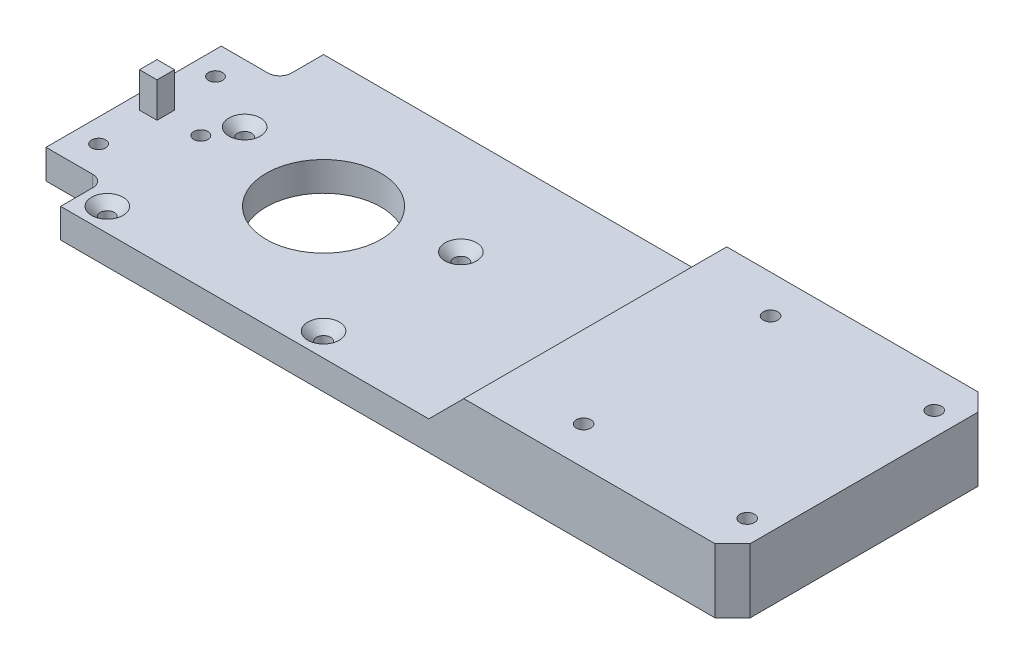
SolidWorks part; units mm, degrees
material "7075-T6, Plate (SS)"
ref_plane "Front Plane" through (0, 0, 0) normal (0, 0, 1) x (1, 0, 0)
ref_plane "Top Plane" through (0, 0, 0) normal (0, 1, 0) x (1, 0, 0)
ref_plane "Right Plane" through (0, 0, 0) normal (1, 0, 0) x (0, 0, -1)
sketch "Sketch1" plane through (0, 0, 0) normal (0, 1, 0) x (1, 0, 0)
  line L1 (0, -22.5) -> (115, -22.5)
  line L2 (0, -22.5) -> (0, 22.5)
  line L3 (0, 22.5) -> (115, 22.5)
  line L4 (115, -22.5) -> (115, 22.5)
  dimension "D1" = 45
  dimension "D2" = 115
extrude "Boss-Extrude1" add sketch "Sketch1" along normal blind 5 contours L2 L3 L4 L1
sketch "Sketch2" plane through (0, 5, 0) normal (0, 1, 0) x (1, 0, 0)
  line L0 (0, -22.5) -> (0, 22.5) construction
  circle A0 centre (22.5, 0) radius 9.8171
  dimension "D2" = 19.6342
  dimension "D1" = 22.5
extrude "Cut-Extrude1" cut sketch "Sketch2" against normal up to next
cosmetic thread "Cosmetic Thread1" parameters "D2"=20.32
hole_wizard "CSK for M2 Countersunk Flat Head Screw1" positions "Sketch3" profile "Sketch4" countersink size "M2" standard "DIN" end condition through all
sketch "Sketch3" plane through (0, 5, 0) normal (0, 1, 0) x (1, 0, 0)
  line L2 (0, -22.5) -> (115, -22.5) construction
  point P6 (4, -18.5)
  point P48 (41, -18.5)
  point P50 (41, 5)
  point P52 (4, 5)
  dimension "D3" = 4
  dimension "D5" = 37
  dimension "D6" = 27.5
sketch "Sketch4" plane through (4, 5, 18.5) normal (1, 0, 0) x (0, 0, 1)
  line L0 (0, 0) -> (0, 5)
  line L1 (0, 5) -> (1.2, 5)
  line L2 (1.2, 5) -> (1.2, 1.5)
  line L3 (1.2, 1.5) -> (2.7, 0)
  line L5 (2.7, 0) -> (0, 0)
  line L6 (-1.2, 1.5) -> (-2.7, 0) construction
  line L11 (0, -6.35) -> (0, 107.95) construction
  dimension "Thru Hole Dia." = 2.4
  dimension "Thru Hole Depth" = 5
  dimension "Near C'Sink Dia." = 5.4
  dimension "Near C'Sink Angle" = 90
sketch "Sketch13" plane through (0, 5, 0) normal (0, 1, 0) x (1, 0, 0)
  line L0 (0, -22.5) -> (115, -22.5) construction
  line L1 (115, 22.5) -> (63, 22.5)
  line L2 (115, 22.5) -> (115, -22.5)
  line L3 (115, -22.5) -> (63, -22.5)
  line L4 (63, 22.5) -> (63, -22.5)
  dimension "D1" = 52
extrude "Boss-Extrude4" add sketch "Sketch13" along normal blind 6
chamfer "Chamfer2" distance 6 angle 45 1 edges at (63, 11, 0)
hole_wizard "M3 Tapped Hole1" positions "Sketch5" profile "Sketch6" tap size "M3" standard "DIN" end condition through all
sketch "Sketch5" plane through (0, 11, 0) normal (0, 1, 0) x (1, 0, 0)
  line L1 (83, 16) -> (111, 16) construction
  line L2 (83, 16) -> (83, -16) construction
  line L3 (83, -16) -> (111, -16) construction
  line L4 (111, 16) -> (111, -16) construction
  circle A0 centre (22.5, 0) radius 9.8171 construction
  point P0 (83, 16)
  point P2 (111, 16)
  point P4 (83, -16)
  point P6 (111, -16)
  point P74 (83, 0)
  point P76 (97, 16)
  dimension "D1" = 74.5
  dimension "D2" = 28
  dimension "D3" = 32
sketch "Sketch6" plane through (83, 11, -16) normal (1, 0, 0) x (0, 0, 1)
  line L0 (0, 0) -> (0, 11)
  line L1 (0, 11) -> (1.25, 11)
  line L2 (1.25, 11) -> (1.25, 0)
  line L5 (1.25, 0) -> (0, 0)
  line L11 (0, -6.35) -> (0, 107.95) construction
  dimension "Thru Tap Drill Dia." = 2.5
  dimension "Thru Tap Drill Depth" = 11
cosmetic thread "Hole Thread7" parameters "D2"=3
cosmetic thread "Hole Thread8" parameters "D2"=3
cosmetic thread "Hole Thread9" parameters "D2"=3
cosmetic thread "Hole Thread10" parameters "D2"=3
chamfer "Chamfer1" distance 3 angle 45 2 edges at (115, 5.5, -22.5) (115, 5.5, 22.5)
sketch "Sketch14" plane through (0, 0, 0) normal (0, 1, 0) x (1, 0, 0)
  line L0 (0, 15) -> (0, -15)
  line L1 (0, -22.5) -> (0, 22.5) construction
  line L2 (0, -15) -> (-10, -15)
  line L3 (-10, -15) -> (-10, 15)
  line L4 (-10, 15) -> (0, 15)
  dimension "D1" = 10
  dimension "D2" = 30
extrude "Boss-Extrude5" add sketch "Sketch14" along normal up to surface (5 mm away) up to face at (31.5, 5, 0)
fillet "Fillet1" radius 2 2 edges at (0, 2.5, 15) (0, 2.5, -15)
hole_wizard "CSK for M2 Countersunk Flat Head Screw2" positions "Sketch15" profile "Sketch16" countersink size "M2" standard "DIN"
sketch "Sketch15" plane through (0, 0, 0) normal (0, -1, 0) x (-1, 0, 0)
  line L0 (0, 17) -> (0, 22.5) construction
  line L1 (10, 15) -> (10, -15) construction
  point P0 (-1.5, 0)
  point P2 (6, -10)
  point P4 (6, 10)
  point P7 (0, 0)
  point P9 (0, 0)
  point P14 (0, 0)
  dimension "D1" = 1.5
  dimension "D2" = 4
  dimension "D3" = 10
  dimension "D4" = 10
sketch "Sketch16" plane through (1.5, 0, 0) normal (1, 0, 0) x (0, 0, -1)
  line L0 (0, 0) -> (0, 5.721)
  line L1 (0, 5.721) -> (1.2, 5)
  line L2 (1.2, 5) -> (1.2, 1.5)
  line L3 (1.2, 1.5) -> (2.7, 0)
  line L5 (2.7, 0) -> (0, 0)
  line L6 (-1.2, 1.5) -> (-2.7, 0) construction
  line L10 (0, 5.721) -> (-1.2, 5) construction
  line L11 (0, -6.35) -> (0, 107.95) construction
  dimension "Hole Dia." = 2.4
  dimension "Hole Depth" = 5
  dimension "Near C'Sink Dia." = 5.4
  dimension "Near C'Sink Angle" = 90
  dimension "Drill Angle" = 118
sketch "Sketch17" plane through (0, 5, 0) normal (0, 1, 0) x (1, 0, 0)
  line L0 (-10, 15) -> (-10, -15) construction
  line L1 (-7.5, 1.5) -> (-4.5, 1.5)
  line L2 (-7.5, 1.5) -> (-7.5, -1.5)
  line L3 (-7.5, -1.5) -> (-4.5, -1.5)
  line L4 (-4.5, 1.5) -> (-4.5, -1.5)
  point P4 (0, 0)
  point P5 (-4.5, 0)
  point P9 (-6, 1.5)
  dimension "D1" = 3
  dimension "D2" = 4
extrude "Boss-Extrude6" add sketch "Sketch17" along normal up to surface (6 mm away) up to face at (83, 11, -14.75)
